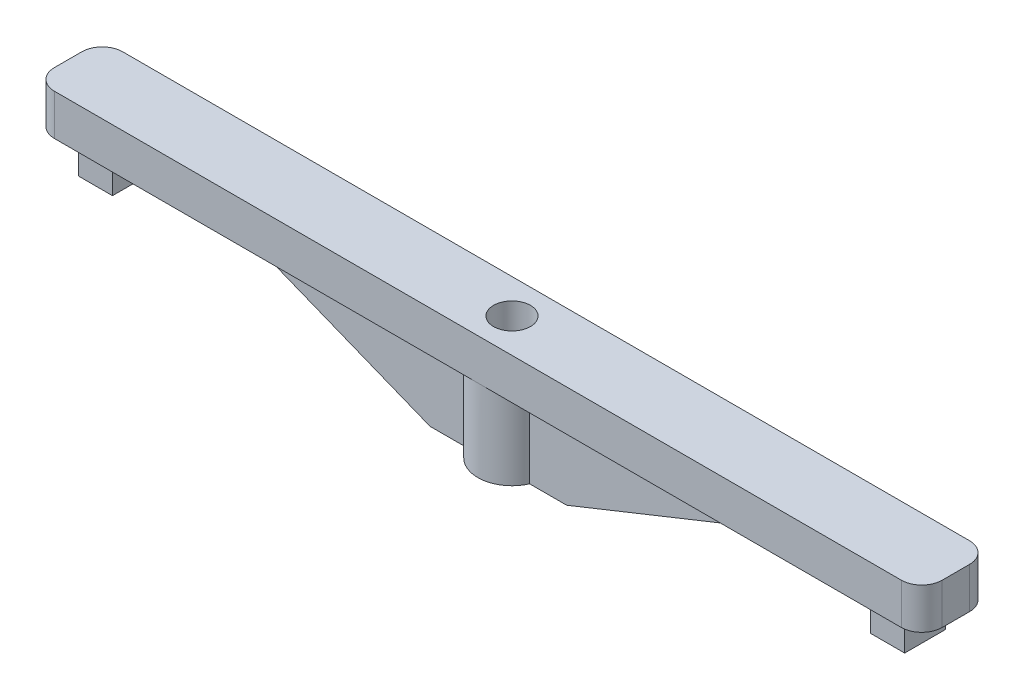
SolidWorks part; units mm, degrees
ref_plane "Front Plane" through (0, 0, 0) normal (0, 0, 1) x (1, 0, 0)
ref_plane "Top Plane" through (0, 0, 0) normal (0, 1, 0) x (1, 0, 0)
ref_plane "Right Plane" through (0, 0, 0) normal (1, 0, 0) x (0, 0, -1)
sketch "Sketch1" plane through (0, 0, 0) normal (0, 1, 0) x (1, 0, 0)
  line L1 (-32.5, 2.5) -> (32.5, 2.5)
  line L2 (-32.5, 2.5) -> (-32.5, -2.5)
  line L3 (-32.5, -2.5) -> (32.5, -2.5)
  line L4 (32.5, 2.5) -> (32.5, -2.5)
  line L5 (-32.5, 2.5) -> (32.5, -2.5) construction
  line L6 (-32.5, -2.5) -> (32.5, 2.5) construction
  point P0 (0, 0)
  dimension "D1" = 5
  dimension "D2" = 65
extrude "body" add sketch "Sketch1" along normal blind 3
sketch "Sketch3" plane through (0, 0, 0) normal (0, -1, 0) x (1, 0, 0)
  line L0 (0, -1.65) -> (0, 1.65) construction
  line L1 (27.75, 1.5) -> (30.25, 1.5)
  line L2 (27.75, 1.5) -> (27.75, -1.5)
  line L3 (27.75, -1.5) -> (30.25, -1.5)
  line L4 (30.25, 1.5) -> (30.25, -1.5)
  line L5 (27.75, 1.5) -> (30.25, -1.5) construction
  line L6 (27.75, -1.5) -> (30.25, 1.5) construction
  line L7 (-27.75, -1.5) -> (-30.25, 1.5) construction
  line L8 (-27.75, 1.5) -> (-30.25, -1.5) construction
  line L9 (-30.25, 1.5) -> (-30.25, -1.5)
  line L10 (-27.75, -1.5) -> (-30.25, -1.5)
  line L11 (-27.75, 1.5) -> (-27.75, -1.5)
  line L12 (-27.75, 1.5) -> (-30.25, 1.5)
  line L13 (1.65, 0) -> (-1.65, 0) construction
  point P0 (29, 0)
  point P11 (-29, 0)
  dimension "D1" = 2.5
  dimension "D2" = 3
  dimension "D3" = 58
extrude "pegs" add sketch "Sketch3" along normal blind 2.5
ref_axis "peg1" through (-29, 0, 0) along (0, -1, 0)
ref_axis "peg2" through (29, 0, 0) along (0, -1, 0)
sketch "Sketch5" plane through (0, 0, 0) normal (0, 0, 1) x (1, 0, 0)
  line L0 (-20, 0) -> (20, 0)
  line L1 (-32.5, 0) -> (32.5, 0) construction
  line L2 (20, 0) -> (5, -6)
  line L3 (5, -6) -> (-5, -6)
  line L4 (-5, -6) -> (-20, 0)
  line L5 (-5, -6) -> (20, 0) construction
  line L6 (5, -6) -> (-20, 0) construction
  point P4 (0, 0)
  dimension "D1" = 10
  dimension "D2" = 40
  dimension "D3" = 6
extrude "web" add sketch "Sketch5" along normal mid plane 2
sketch "Sketch6" plane through (0, 0, 0) normal (0, -1, 0) x (1, 0, 0)
  line L0 (32.5, -2.5) -> (-32.5, -2.5) construction
  circle A0 centre (0, 0) radius 2.5
extrude "hole-boss" add sketch "Sketch6" along normal up to surface (6 mm away) up to face at (0, -6, 0)
hole_wizard "M2.5 Clearance Hole1" positions "Sketch7" profile "Sketch8" hole size "M2.5" standard "ISO" end condition through all
sketch "Sketch7" plane through (0, -6, 0) normal (0, -1, 0) x (-1, 0, 0)
  point P0 (0, 0)
sketch "Sketch8" plane through (0, -6, 0) normal (1, 0, 0) x (0, 0, -1)
  line L0 (0, 0) -> (0, 9)
  line L1 (0, 9) -> (1.35, 9)
  line L2 (1.35, 9) -> (1.35, 0.4)
  line L3 (1.35, 0.4) -> (1.75, 0)
  line L5 (1.75, 0) -> (0, 0)
  line L6 (-1.35, 0.4) -> (-1.75, 0) construction
  line L11 (0, -6.35) -> (0, 107.95) construction
  dimension "Thru Hole Dia." = 2.7
  dimension "Thru Hole Depth" = 9
  dimension "Near C'Sink Dia." = 3.5
  dimension "Near C'Sink Angle" = 90
fillet "Fillet1" radius 1.5 4 edges at (32.5, 1.5, -2.5) (32.5, 1.5, 2.5) (-32.5, 1.5, 2.5) (-32.5, 1.5, -2.5)
fillet "Fillet2" radius 1 4 edges at (29, 0, -1.5) (29, 0, 1.5) (-29, 0, 1.5) (-29, 0, -1.5)
fillet "Fillet3" radius 1 4 edges at (11.1456, 0, 1) (-11.1456, 0, 1) (11.1456, 0, -1) (-11.1456, 0, -1)
